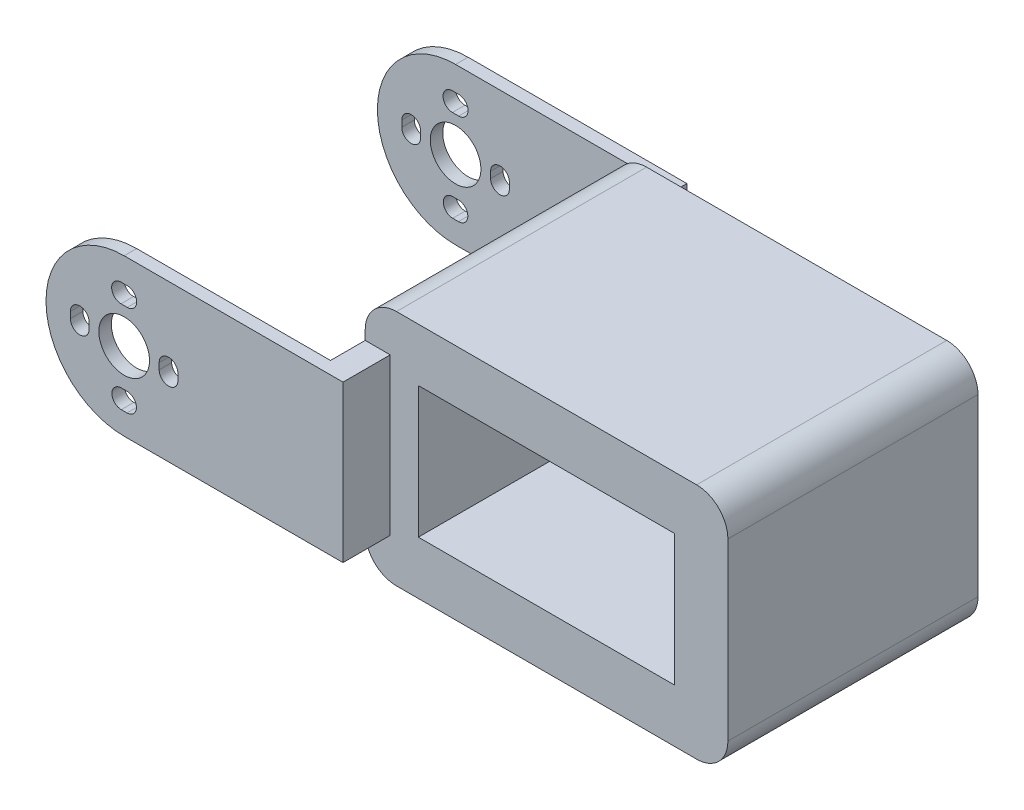
SolidWorks part; units mm, degrees
ref_plane "前基準面" through (0, 0, 0) normal (0, 0, 1) x (1, 0, 0)
ref_plane "上基準面" through (0, 0, 0) normal (0, 1, 0) x (1, 0, 0)
ref_plane "右基準面" through (0, 0, 0) normal (1, 0, 0) x (0, 0, -1)
sketch "Sketch1" plane through (0, 0, 0) normal (0, 0, 1) x (1, 0, 0)
  line L0 (-29.0958, -6.1361) -> (28.9042, -6.1361) construction
  line L1 (-20.5958, 4.3639) -> (20.4042, 4.3639)
  line L2 (-20.5958, 4.3639) -> (-20.5958, -16.6361)
  line L3 (-20.5958, -16.6361) -> (20.4042, -16.6361)
  line L4 (20.4042, 4.3639) -> (20.4042, -16.6361)
  line L5 (-29.0958, 12.8639) -> (28.9042, 12.8639)
  line L6 (-29.0958, 12.8639) -> (-29.0958, -25.1361)
  line L7 (-29.0958, -25.1361) -> (28.9042, -25.1361)
  line L8 (28.9042, 12.8639) -> (28.9042, -25.1361)
  line L9 (-0.0958, 12.8639) -> (-0.0958, -25.1361) construction
  line L10 (20.4042, -6.1361) -> (-20.5958, -6.1361) construction
  line L11 (-0.0958, 4.3639) -> (-0.0958, -16.6361) construction
  point P16 (-0.0958, -6.1361)
  point P17 (-0.0958, -6.1361)
  dimension "D1" = 21
  dimension "D2" = 41
  dimension "D3" = 58
  dimension "D4" = 38
extrude "Boss-Extrude1" add sketch "Sketch1" along normal blind 40
sketch "Sketch2" plane through (0, 0, 40) normal (0, 0, 1) x (1, 0, 0)
  line L0 (-20.5958, -6.1361) -> (-29.0958, -6.1361) construction
  line L2 (-20.5958, 4.3639) -> (-20.5958, -16.6361) construction
  line L3 (-29.0958, 12.8639) -> (-29.0958, -25.1361) construction
  line L4 (-25.0958, -6.1361) -> (-29.4032, -6.1361) construction
  line L5 (-29.0958, 6.3639) -> (-25.0958, 6.3639)
  line L6 (-29.0958, 6.3639) -> (-29.0958, -18.6361)
  line L7 (-29.0958, -18.6361) -> (-25.0958, -18.6361)
  line L8 (-25.0958, 6.3639) -> (-25.0958, -18.6361)
  point P13 (-24.8458, -6.1361)
  dimension "D1" = 25
  dimension "D2" = 4
extrude "Boss-Extrude2" add sketch "Sketch2" along normal blind 5.55
extrude "Boss-Extrude3" add sketch "Sketch2<2>" against normal blind 45.55
sketch "Sketch2<2>" plane through (0, 0, 40) normal (0, 0, 1) x (1, 0, 0) same geometry as "Sketch2"
sketch "Sketch3" plane through (0, 0, 45.55) normal (0, 0, 1) x (1, 0, 0)
  line L0 (-60.5958, 0.9639) -> (-59.5958, 0.9639) construction
  line L1 (-25.0958, 6.3639) -> (-60.0958, 6.3639)
  line L2 (-25.0958, 6.3639) -> (-25.0958, -18.6361)
  line L3 (-25.0958, -18.6361) -> (-60.0958, -18.6361)
  line L4 (-60.0958, 6.3639) -> (-60.0958, -18.6361)
  line L5 (-60.5958, 2.4639) -> (-59.5958, 2.4639)
  line L6 (-60.5958, -0.5361) -> (-59.5958, -0.5361)
  line L7 (-60.0958, 6.3639) -> (-60.0958, -18.6361) construction
  line L8 (-60.5559, -13.6762) -> (-59.6357, -13.6762) construction
  line L9 (-60.5559, -12.1762) -> (-59.6357, -12.1762)
  line L10 (-60.5559, -15.1762) -> (-59.6357, -15.1762)
  line L11 (-60.0958, -6.1361) -> (-72.5958, -6.1361) construction
  line L12 (-67.1958, -5.6361) -> (-67.1958, -6.6361) construction
  line L15 (-65.6958, -5.6361) -> (-65.6958, -6.6361)
  line L16 (-68.6958, -5.6361) -> (-68.6958, -6.6361)
  line L17 (-52.9958, -5.6361) -> (-52.9958, -6.6361) construction
  line L18 (-51.4958, -5.6361) -> (-51.4958, -6.6361)
  line L19 (-54.4958, -5.6361) -> (-54.4958, -6.6361)
  line L20 (-60.0958, -6.1361) -> (-25.0958, -6.1361) construction
  arc A0 (-60.0958, 6.3639) -> (-60.0958, -18.6361) centre (-60.0958, -6.1361) ccw
  circle A1 centre (-60.0958, -6.1361) radius 4.05
  arc A3 (-60.5958, 2.4639) -> (-60.5958, -0.5361) centre (-60.5958, 0.9639) ccw
  arc A4 (-59.5958, -0.5361) -> (-59.5958, 2.4639) centre (-59.5958, 0.9639) ccw
  arc A5 (-60.5559, -12.1762) -> (-60.5559, -15.1762) centre (-60.5559, -13.6762) ccw
  arc A6 (-59.6357, -15.1762) -> (-59.6357, -12.1762) centre (-59.6357, -13.6762) ccw
  arc A9 (-65.6958, -5.6361) -> (-68.6958, -5.6361) centre (-67.1958, -5.6361) ccw
  arc A10 (-68.6958, -6.6361) -> (-65.6958, -6.6361) centre (-67.1958, -6.6361) ccw
  arc A11 (-51.4958, -5.6361) -> (-54.4958, -5.6361) centre (-52.9958, -5.6361) ccw
  arc A12 (-54.4958, -6.6361) -> (-51.4958, -6.6361) centre (-52.9958, -6.6361) ccw
  point P9 (-60.0958, 0.9639)
  point P14 (-58.0958, 0.9639)
  point P15 (-62.0958, 0.9639)
  point P19 (-60.0958, -13.6762)
  point P25 (-67.1958, -6.1361)
  point P31 (-67.1958, -4.1361)
  point P32 (-67.1958, -8.1361)
  point P33 (-43.4958, -6.1361)
  point P34 (-65.6958, -6.1361)
  point P37 (-52.9958, -6.1361)
  point P42 (-52.9958, -4.1361)
  point P43 (-52.9958, -8.1361)
  line M15 (-29.0958, 6.3639) -> (-29.0958, -18.6361)
  line M16 (-29.0958, -18.6361) -> (-25.0958, -18.6361)
  line M17 (-25.0958, -18.6361) -> (-25.0958, 6.3639)
  line M18 (-25.0958, 6.3639) -> (-29.0958, 6.3639)
  dimension "D2" = 4
  dimension "D10" = 5.6
  dimension "D9" = 4
  dimension "D1" = 35
  dimension "D3" = 3
  dimension "D4" = 5.6
  dimension "D5" = 25
  dimension "D6" = 6.0402
  dimension "D7" = 0
  dimension "D8" = 3
  dimension "D11" = 5.6
  dimension "D12" = 3
  dimension "D13" = 4
extrude "Boss-Extrude6" add sketch "Sketch3" along normal blind 2 contours A5 L9 L4 A1 L6 A3 L5 A0 L10 A10 L16 A9 L15 | A6 L10 L4 L3 L1 L5 A4 L6 A1 L9 A12 L19 A11 L18 M15 | M18 M15 M16 M17 region at (-27.0958, -6.1361, 45.55) region at (-43.7932, -6.1343, 45.55) region at (-60.3753, 4.4139, 45.55)
extrude "Boss-Extrude7" add sketch "Sketch3<8>" against normal blind 53 contours A5 L9 L4 A1 L6 A3 L5 A0 L10 A10 L16 A9 L15 | A6 L10 L4 L3 L1 L5 A4 L6 A1 L9 A12 L19 A11 L18 M15 | M18 M15 M16 M17 region at (-27.0958, -6.1361, 45.55) region at (-43.7932, -6.1343, 45.55) region at (-60.3753, 4.4139, 45.55)
sketch "Sketch3<8>" plane through (0, 0, 45.55) normal (0, 0, 1) x (1, 0, 0) same geometry as "Sketch3"
extrude "Cut-Extrude1" cut sketch "Sketch3<11>" against normal blind 51 contours A6 L10 L4 L3 L1 L5 A4 L6 A1 L9 A12 L19 A11 L18 M15 | A5 L9 L4 A1 L6 A3 L5 A0 L10 A10 L16 A9 L15 region at (-43.7932, -6.1343, 45.55) region at (-60.3753, 4.4139, 45.55)
sketch "Sketch3<11>" plane through (0, 0, 45.55) normal (0, 0, 1) x (1, 0, 0) same geometry as "Sketch3"
fillet "Fillet2" radius 5 1 edges at (28.9042, 12.8639, 20) type face fillet first side face at (-0.0958, 12.8639, 20) second side face at (28.9042, -6.1361, 20)
fillet "Fillet3" radius 5 1 edges at (28.9042, -25.1361, 20) type face fillet first side face at (28.9042, -8.6361, 20) second side face at (-0.0958, -25.1361, 20)
fillet "Fillet4" radius 5 1 edges at (-29.0958, 12.8639, 20) type face fillet first side face at (-29.0958, -6.1361, 20.0167) second side face at (-2.5958, 12.8639, 20)
fillet "Fillet5" radius 5 1 edges at (-29.0958, -25.1361, 20) type face fillet first side face at (-2.5958, -25.1361, 20) second side face at (-29.0958, -6.9694, 20.0167)
